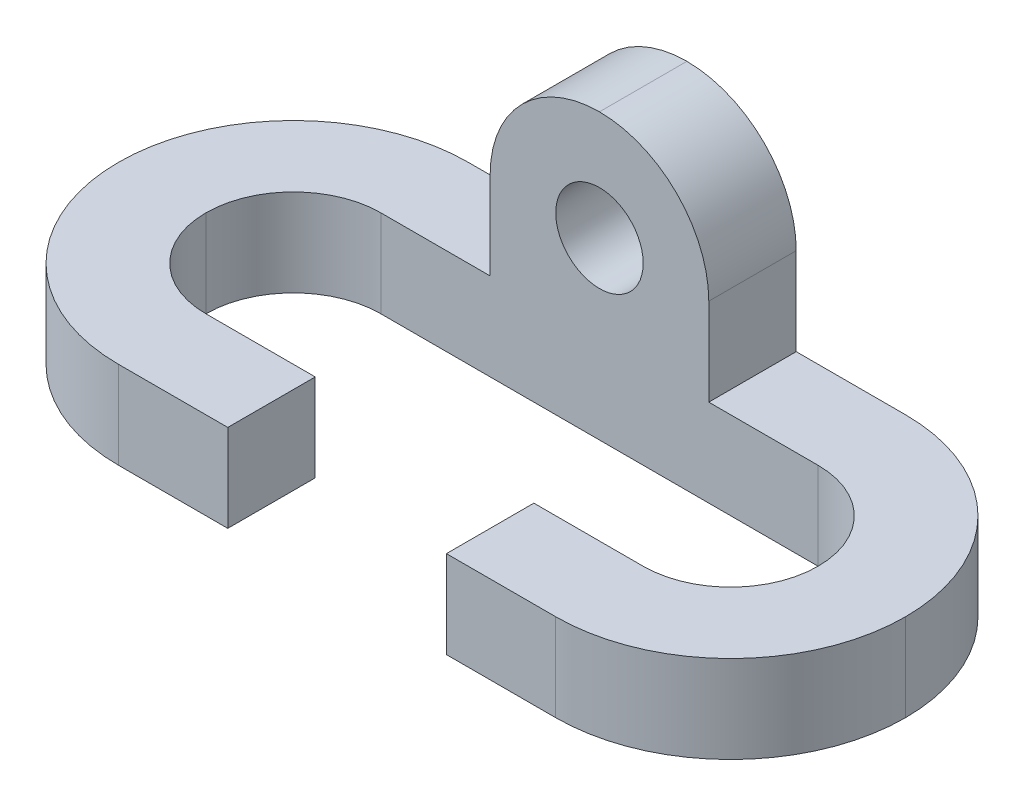
SolidWorks part; units mm, degrees
ref_plane "Front Plane" through (0, 0, 0) normal (0, 0, 1) x (1, 0, 0)
ref_plane "Top Plane" through (0, 0, 0) normal (0, 1, 0) x (1, 0, 0)
ref_plane "Right Plane" through (0, 0, 0) normal (1, 0, 0) x (0, 0, -1)
sketch "Sketch2" plane through (0, 0, 0) normal (0, 1, 0) x (1, 0, 0)
  line L0 (12.7, 12.7) -> (12.7, 38.1)
  line L1 (0, 0) -> (114.3, 0)
  line L2 (0, 0) -> (0, 50.8)
  line L3 (0, 50.8) -> (114.3, 50.8)
  line L4 (114.3, 0) -> (114.3, 50.8)
  line L5 (12.7, 38.1) -> (101.6, 38.1)
  line L6 (101.6, 12.7) -> (101.6, 38.1)
  line L7 (12.7, 12.7) -> (101.6, 12.7)
  dimension "D1" = 12.7
  dimension "D2" = 50.8
  dimension "D3" = 114.3
extrude "Boss-Extrude1" add sketch "Sketch2" against normal blind 12.7
fillet "Fillet3" radius 25.4 4 edges at (0, -6.35, 0) (0, -6.35, -50.8) (114.3, -6.35, -50.8) (114.3, -6.35, 0)
fillet "Fillet4" radius 12.7 4 edges at (12.7, -6.35, -12.7) (101.6, -6.35, -12.7) (101.6, -6.35, -38.1) (12.7, -6.35, -38.1)
sketch "Sketch5" plane through (0, 0, 0) normal (0, 1, 0) x (1, 0, 0)
  line L0 (88.9, 50.8) -> (25.4, 50.8) construction
  line L1 (41.275, 50.8) -> (73.025, 50.8)
  line L2 (41.275, 50.8) -> (41.275, 38.1)
  line L3 (41.275, 38.1) -> (73.025, 38.1)
  line L4 (73.025, 50.8) -> (73.025, 38.1)
  line L5 (88.9, 38.1) -> (25.4, 38.1) construction
  dimension "D1" = 31.75
  dimension "D2" = 15.875
extrude "Boss-Extrude2" add sketch "Sketch5" along normal blind 28.575
fillet "Fillet5" radius 15.875 2 edges at (41.275, 28.575, -44.45) (73.025, 28.575, -44.45)
sketch "Sketch6" plane through (0, 0, -38.1) normal (0, 0, 1) x (1, 0, 0)
  line L0 (88.9, -12.7) -> (25.4, -12.7) construction
  line L1 (41.275, 12.7) -> (41.275, 0) construction
  circle A0 centre (57.15, 12.7) radius 6.35
  point P4 (0, 0)
  dimension "D2" = 12.7
  dimension "D1" = 25.4
  dimension "D3" = 15.875
extrude "Cut-Extrude1" cut sketch "Sketch6" against normal through all
sketch "Sketch7" plane through (0, 0, 0) normal (0, 1, 0) x (1, 0, 0)
  line L6 (25.4, 12.7) -> (88.9, 12.7) construction
  line L7 (41.275, 12.7) -> (73.025, 12.7)
  line L8 (41.275, 12.7) -> (41.275, 0)
  line L9 (41.275, 0) -> (73.025, 0)
  line L10 (73.025, 12.7) -> (73.025, 0)
  line L11 (25.4, 0) -> (88.9, 0) construction
  dimension "D1" = 31.75
  dimension "D2" = 15.875
extrude "Cut-Extrude2" cut sketch "Sketch7" against normal through all
